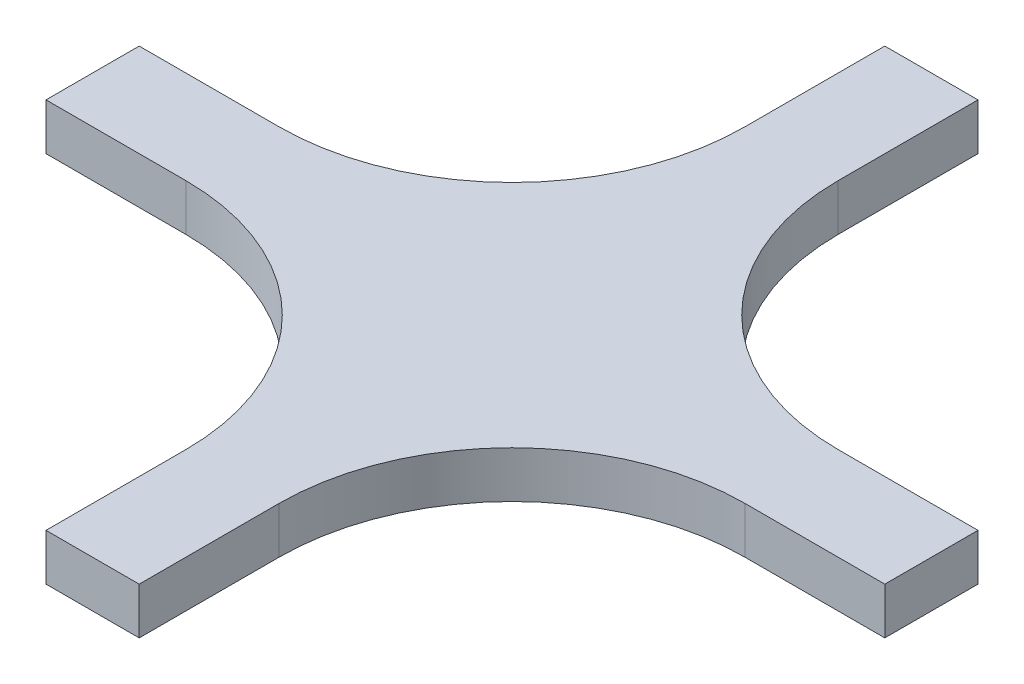
SolidWorks part; units mm, degrees
ref_plane "Front Plane" through (0, 0, 0) normal (0, 0, 1) x (1, 0, 0)
ref_plane "Top Plane" through (0, 0, 0) normal (0, 1, 0) x (1, 0, 0)
ref_plane "Right Plane" through (0, 0, 0) normal (1, 0, 0) x (0, 0, -1)
sketch "Sketch1" plane through (0, 0, 0) normal (0, 1, 0) x (1, 0, 0)
  line L0 (171.3318, 0) -> (-229.5995, 0) construction
  line L5 (0, 176.4778) -> (0, -135.7808) construction
  line L6 (-152.4, 25.4) -> (-228.6, 25.4)
  line L7 (-228.6, 25.4) -> (-228.6, -25.4)
  line L8 (-25.4, 152.4) -> (-25.4, 228.6)
  line L9 (-25.4, 228.6) -> (25.4, 228.6)
  line L10 (25.4, 152.4) -> (25.4, 228.6)
  line L11 (228.6, 25.4) -> (228.6, -25.4)
  line L12 (152.4, 25.4) -> (228.6, 25.4)
  line L13 (152.4, -25.4) -> (228.6, -25.4)
  line L14 (25.4, -152.4) -> (25.4, -228.6)
  line L15 (-25.4, -228.6) -> (25.4, -228.6)
  line L16 (-25.4, -152.4) -> (-25.4, -228.6)
  line L17 (-152.4, -25.4) -> (-228.6, -25.4)
  arc A0 (-152.4, 25.4) -> (-25.4, 152.4) centre (-152.4, 152.4) ccw
  arc A1 (152.4, 25.4) -> (25.4, 152.4) centre (152.4, 152.4) cw
  arc A2 (152.4, -25.4) -> (25.4, -152.4) centre (152.4, -152.4) ccw
  arc A3 (-152.4, -25.4) -> (-25.4, -152.4) centre (-152.4, -152.4) cw
  point P0 (0, 0)
  point P17 (0, 228.6)
  point P23 (228.6, 0)
  point P29 (-228.6, 0)
  dimension "D1" = 127
  dimension "D2" = 76.2
  dimension "D3" = 50.8
extrude "Boss-Extrude1" add sketch "Sketch1" along normal blind 25.4
